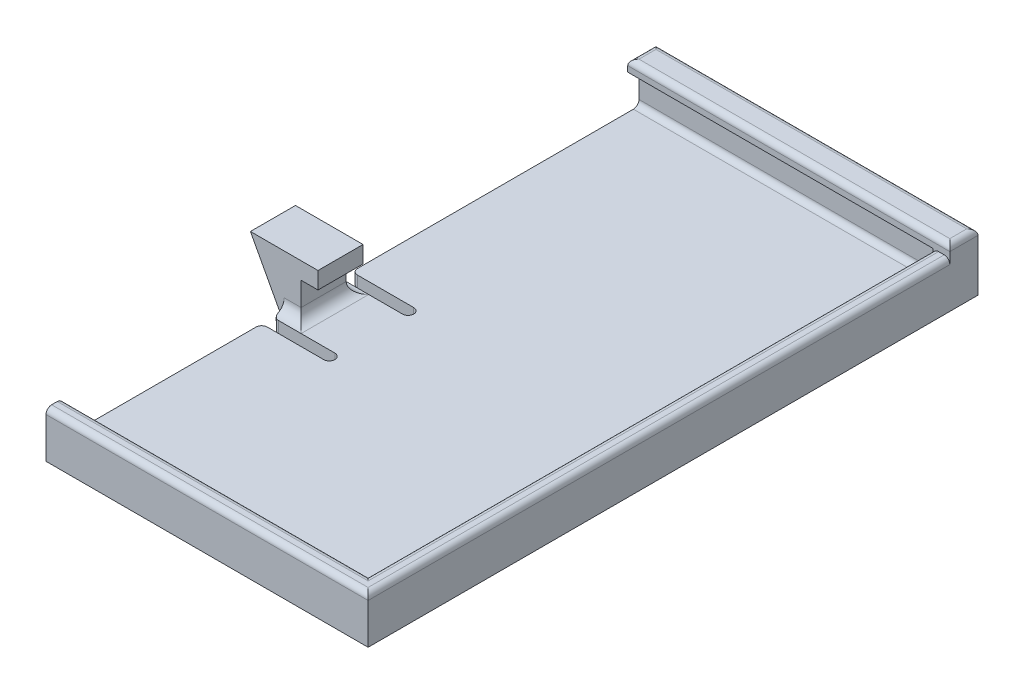
SolidWorks part; units mm, degrees
note: The reader was unsure of these and kept them because the rebuilt part matched: shared geometry of "Sketch2<3>".
ref_plane "Front Plane" through (0, 0, 0) normal (0, 0, 1) x (1, 0, 0)
ref_plane "Top Plane" through (0, 0, 0) normal (0, 1, 0) x (1, 0, 0)
ref_plane "Right Plane" through (0, 0, 0) normal (1, 0, 0) x (0, 0, -1)
sketch "Board Outline" plane through (0, 0, 0) normal (0, 1, 0) x (1, 0, 0)
  line L1 (-12.7, 25.375) -> (12.7, 25.375)
  line L2 (-12.7, 25.375) -> (-12.7, -25.375)
  line L3 (-12.7, -25.375) -> (12.7, -25.375)
  line L4 (12.7, 25.375) -> (12.7, -25.375)
  line L5 (-12.7, 25.375) -> (12.7, -25.375) construction
  line L6 (-12.7, -25.375) -> (12.7, 25.375) construction
  point P0 (0, 0)
  dimension "D1" = 50.75
  dimension "D2" = 25.4
sketch "Sketch2" plane through (0, 0, 0) normal (0, 1, 0) x (1, 0, 0)
  line L0 (-12.7, 25.375) -> (12.7, -25.375) construction
  line L1 (-14.3001, 27.075) -> (14.3001, 27.075)
  line L2 (-14.3001, 27.075) -> (-14.3001, -27.075)
  line L3 (-14.3001, -27.075) -> (14.3001, -27.075)
  line L4 (14.3001, 27.075) -> (14.3001, -27.075)
  line L5 (-14.3001, 27.075) -> (14.3001, -27.075) construction
  line L6 (-14.3001, -27.075) -> (14.3001, 27.075) construction
  line L7 (-12.8001, 25.575) -> (12.8001, 25.575)
  line L8 (-12.8001, 25.575) -> (-12.8001, -25.575)
  line L9 (-12.8001, -25.575) -> (12.8001, -25.575)
  line L10 (12.8001, 25.575) -> (12.8001, -25.575)
  line L11 (-12.8001, 25.575) -> (12.8001, -25.575) construction
  line L12 (-12.8001, -25.575) -> (12.8001, 25.575) construction
  line L13 (-12.7, -25.375) -> (12.7, -25.375) construction
  point P0 (0, 0)
  point P6 (0, 0)
  point P11 (16.355, -29.8983)
  point P12 (0, 0)
  point P13 (13.4315, -27.9281)
  dimension "D1" = 0.2
  dimension "D2" = 1.5
  dimension "D3" = 1.5
extrude "Boss-Extrude1" add sketch "Sketch2" against normal blind 1 contours L4 L3 L2 L1
extrude "Boss-Extrude2" add sketch "Sketch2<3>" along normal blind 3.1 contours L8 L9 L10 L7
sketch "Sketch2<3>" plane through (0, 0, 0) normal (0, 1, 0) x (1, 0, 0) same geometry as "Sketch2"
sketch "Sketch3" plane through (0, 3.1, 0) normal (0, 1, 0) x (1, 0, 0)
  line L0 (-12.8001, 25.575) -> (12.8001, 25.575) construction
  line L5 (6.3001, 25.575) -> (-19.5858, 25.575)
  line L6 (6.3001, 25.575) -> (6.3001, -25.575)
  line L7 (6.3001, -25.575) -> (-19.5858, -25.575)
  line L8 (-19.5858, 25.575) -> (-19.5858, -25.575)
  line L9 (-12.8001, -25.575) -> (12.8001, -25.575) construction
  dimension "D1" = 8
extrude "Cut-Extrude1" cut sketch "Sketch3" against normal up to surface (3.1 mm away) up to face at (0, 0, 0)
ref_plane "Plane1" through (0, 0, 1.925) normal (0, 0, 1) x (1, 0, 0)
sketch "Sketch4" plane through (0, 0, 1.925) normal (0, 0, 1) x (1, 0, 0)
  line L0 (-14.3001, 0) -> (-12.8001, 0)
  line L1 (-12.8001, 0) -> (-12.8001, 3.1)
  line L2 (-12.8001, 3.1) -> (-11.3001, 3.1)
  line L3 (-11.3001, 3.1) -> (-11.3001, 4.6)
  line L4 (-11.3001, 4.6) -> (-17.3001, 4.6)
  line L5 (-17.3001, 4.6) -> (-14.3001, -1)
  line L6 (-14.3001, -1) -> (-14.3001, 0)
  point P3 (0, 0)
  point P9 (0, 0)
  dimension "D1" = 1.5
  dimension "D2" = 3.1
  dimension "D3" = 1.5
  dimension "D4" = 1.5
  dimension "D5" = 6
extrude "Boss-Extrude3" add sketch "Sketch4" along normal blind 4
sketch "Sketch5" plane through (0, 3.1, 0) normal (0, 1, 0) x (1, 0, 0)
  line L0 (14.3001, -27.075) -> (14.3001, 27.075) construction
  line L1 (-14.3001, 27.075) -> (14.3001, 27.075)
  line L2 (-14.3001, 27.075) -> (-14.3001, 24.575)
  line L3 (-14.3001, 24.575) -> (14.3001, 24.575)
  line L4 (14.3001, 27.075) -> (14.3001, 24.575)
  line L5 (12.8001, 25.575) -> (-14.3001, 25.575) construction
  dimension "D1" = 1
extrude "Boss-Extrude4" add sketch "Sketch5" along normal blind 1
fillet "Fillet1" radius 1 3 edges at (-13.5501, 0, 1.925) (-13.5501, 0, 5.925) (-12.8001, 0, 3.925)
fillet "Fillet2" radius 0.5 8 edges at (-14.3001, 4.1, -25.825) (14.3001, 4.1, -25.825) (0, 4.1, -27.075) (0, 4.1, -24.575) (14.3001, 3.1, 1.25) (12.8001, 3.1, 0.5) (0, 3.1, 27.075) (-0.75, 3.1, 25.575)
sketch "Sketch7" plane through (0, 0, 0) normal (0, 1, 0) x (1, 0, 0)
  line L1 (-14.3001, -0.925) -> (-8.3001, -0.925)
  line L2 (-14.3001, -0.925) -> (-14.3001, 0.075)
  line L3 (-14.3001, 0.075) -> (-8.3001, 0.075)
  line L4 (-8.3001, -0.925) -> (-8.3001, 0.075)
  line L5 (-14.3001, -6.925) -> (-8.3001, -6.925)
  line L6 (-14.3001, -6.925) -> (-14.3001, -7.925)
  line L7 (-14.3001, -7.925) -> (-8.3001, -7.925)
  line L8 (-8.3001, -6.925) -> (-8.3001, -7.925)
  dimension "D1" = 1
  dimension "D2" = 6
  dimension "D3" = 1
extrude "Cut-Extrude2" cut sketch "Sketch7" against normal blind 1
fillet "Fillet3" radius 0.5 12 edges at (-14.3001, -0.5, 0.925) (-14.3001, -0.5, -0.075) (-8.3001, -1, 0.425) (-8.3001, -0.5, -0.075) (-8.3001, -0.5, 0.925) (-8.3001, 0, 0.425) (-14.3001, -0.5, 7.925) (-14.3001, -0.5, 6.925) (-8.3001, -1, 7.425) (-8.3001, -0.5, 6.925) (-8.3001, -0.5, 7.925) (-8.3001, 0, 7.425)
fillet "Fillet4" radius 0.5 3 edges at (-0.75, 0, 25.575) (12.8001, 0, 0) (-0.75, 0, -25.575)
